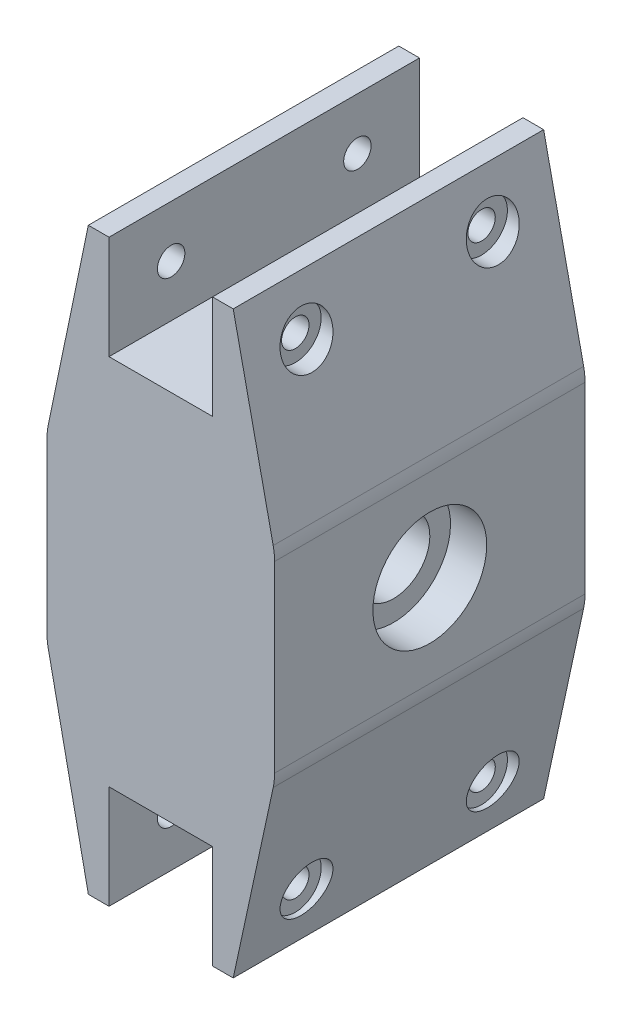
SolidWorks part; units mm, degrees
ref_plane "Front" through (0, 0, 0) normal (0, 0, 1) x (1, 0, 0)
ref_plane "Top" through (0, 0, 0) normal (0, 1, 0) x (1, 0, 0)
ref_plane "Right" through (0, 0, 0) normal (1, 0, 0) x (0, 0, -1)
sketch "Sketch1" plane through (0, 0, 0) normal (0, 0, 1) x (1, 0, 0)
  line L0 (-10, 36) -> (-10, 56)
  line L1 (-10, -36) -> (10, -36)
  line L2 (-10, -36) -> (-10, 36)
  line L3 (-10, 36) -> (10, 36)
  line L4 (10, -36) -> (10, 36)
  line L5 (-10, -36) -> (10, 36) construction
  line L6 (-10, 36) -> (10, -36) construction
  line L7 (-10, 56) -> (-14, 56)
  line L8 (-14, 56) -> (-22, 17.5)
  line L9 (-22, 17.5) -> (-22, -17.5)
  line L10 (-22, -17.5) -> (-14, -56)
  line L11 (-14, -56) -> (-10, -56)
  line L12 (-10, -56) -> (-10, -36)
  line L13 (0, 0) -> (0, 36) construction
  line L14 (10, -56) -> (10, -36)
  line L15 (14, -56) -> (10, -56)
  line L16 (22, -19) -> (14, -56)
  line L17 (22, 19) -> (22, -19)
  line L18 (14, 56) -> (22, 19)
  line L19 (10, 56) -> (14, 56)
  line L20 (10, 36) -> (10, 56)
  line L21 (14, 56) -> (14, -56)
  point P0 (0, 0)
  dimension "D1" = 72
  dimension "D2" = 20
  dimension "D3" = 4
  dimension "D4" = 20
  dimension "D5" = 20
  dimension "D6" = 4
  dimension "D7" = 12
  dimension "D8" = 35
  dimension "D9" = 17.5
  dimension "D10" = 12
  dimension "D11" = 38
  dimension "D12" = 19
extrude "Boss-Extrude1" add sketch "Sketch1" along normal blind 60 contours L20 L4 L14 L15 L16 L17 L18 L19 | L1 L4 L3 L2 | L11 L12 L2 L0 L7 L8 L9 L10 | L18 L21 L16 L17 region at (-15.009, 0, 0) region at (0, 0, 0) region at (12, 0, 0) region at (17.3422, 0, 0)
sketch "Sketch2" plane through (-22, 0, 0) normal (-1, 0, 0) x (0, 0, 1)
  line L0 (0, 0) -> (60, 0) construction
  line L1 (60, 17.5) -> (60, -17.5) construction
  circle A0 centre (30, 0) radius 7
  dimension "D1" = 14
extrude "Cut-Extrude1" cut sketch "Sketch2" against normal through all
sketch "Sketch3" plane through (-22, 0, 0) normal (-1, 0, 0) x (0, 0, 1)
  circle A0 centre (30, 0) radius 11
  dimension "D1" = 22
extrude "Cut-Extrude2" cut sketch "Sketch3" against normal blind 7
sketch "Sketch4" plane through (22, 0, 0) normal (1, 0, 0) x (0, 0, -1)
  circle A0 centre (-30, 0) radius 11 construction
  circle A1 centre (-30, 0) radius 11
extrude "Cut-Extrude3" cut sketch "Sketch4" against normal blind 7
ref_plane "Plane1" through (-18, 0, 0) normal (1, 0, 0) x (0, 0, -1)
sketch "Sketch5" plane through (-18, 0, 0) normal (1, 0, 0) x (0, 0, -1)
  line L0 (-60, 56) -> (0, 56) construction
  line L1 (0, 56) -> (0, 17.5) construction
  line L2 (-60, 56) -> (-60, 17.5) construction
  line L3 (-30, 56) -> (-30, 46) construction
  circle A0 centre (-12, 46) radius 2.65
  circle A1 centre (-48, 46) radius 2.65
  dimension "D1" = 10
  dimension "D3" = 12
  dimension "D5" = 5.3
  dimension "D6" = 5.3
  dimension "D2" = 12
extrude "Cut-Extrude4" cut sketch "Sketch5" along normal through all
sketch "Sketch6" plane through (-18, 0, 0) normal (1, 0, 0) x (0, 0, -1)
  circle A0 centre (-12, 46) radius 5
  circle A2 centre (-48, 46) radius 5
  dimension "D1" = 10
  dimension "D3" = 10
extrude "Cut-Extrude5" cut sketch "Sketch6" along normal blind 4
mirror "Mirror3" about plane through (0, 0, 0) normal (0, 1, 0) of "Cut-Extrude5", "Cut-Extrude4"
fillet "Fillet1" radius 12 4 edges at (-22, -17.5, 30) (-22, 17.5, 30) (22, -19, 30) (22, 19, 30)
ref_plane "Plane2" through (18, 0, 0) normal (-1, 0, 0) x (0, 0, 1)
sketch "Sketch7" plane through (18, 0, 0) normal (-1, 0, 0) x (0, 0, 1)
  circle A0 centre (12, 46) radius 5 construction
  circle A1 centre (48, 46) radius 5 construction
  circle A2 centre (12, 46) radius 5
  circle A3 centre (48, 46) radius 5
extrude "Cut-Extrude6" cut sketch "Sketch7" along normal blind 4
mirror "Mirror5" about plane through (0, 0, 0) normal (0, 1, 0) of "Cut-Extrude6"
